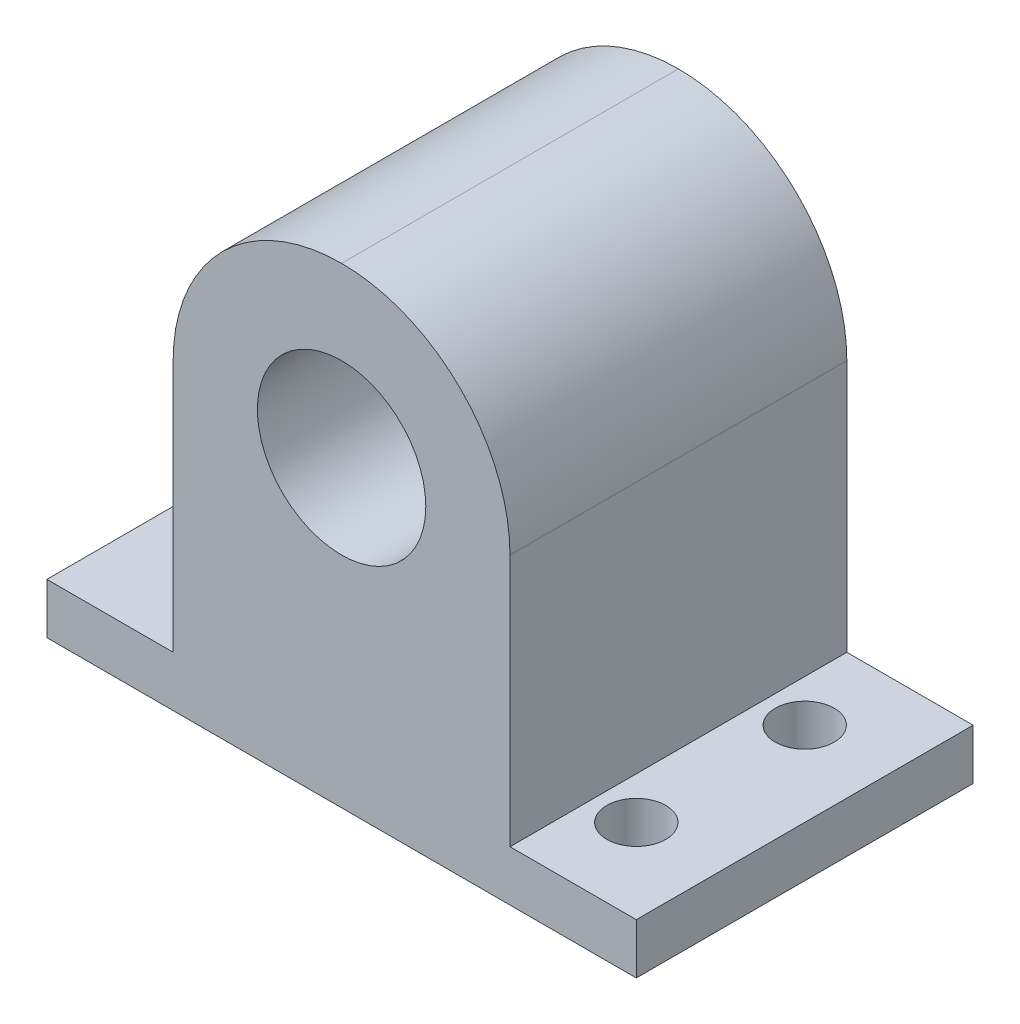
SolidWorks part; units mm, degrees
ref_plane "前视基准面" through (0, 0, 0) normal (0, 0, 1) x (1, 0, 0)
ref_plane "上视基准面" through (0, 0, 0) normal (0, 1, 0) x (1, 0, 0)
ref_plane "右视基准面" through (0, 0, 0) normal (1, 0, 0) x (0, 0, -1)
other "Configuration Table"
sketch "草图1" plane through (0, 0, 0) normal (0, 0, 1) x (1, 0, 0)
  line L1 (0, 0) -> (35, 0)
  line L2 (0, 0) -> (0, 3)
  line L3 (0, 3) -> (35, 3)
  line L4 (35, 0) -> (35, 3)
  line L5 (7.5, 3) -> (27.5, 3)
  line L6 (7.5, 3) -> (7.5, 28)
  line L7 (7.5, 28) -> (27.5, 28)
  line L8 (27.5, 3) -> (27.5, 28)
  dimension "D1" = 35
  dimension "D2" = 3
  dimension "D3" = 7.5
  dimension "D4" = 7.5
  dimension "D5" = 25
extrude "凸台-拉伸1" add sketch "草图1" along normal blind 20 contours L1 L4 L3 L2 | L7 L8 L5 L6 region at (17.5, 1.5, 0)
fillet "圆角1" radius 10 1 edges at (27.5, 28, 10)
fillet "圆角2" radius 10 1 edges at (7.5, 28, 10)
sketch "草图2" plane through (0, 0, 20) normal (0, 0, 1) x (1, 0, 0)
  line L2 (0, 3) -> (7.5, 3) construction
  line L3 (27.5, 3) -> (27.5, 18) construction
  circle A0 centre (17.5, 18) radius 5
  dimension "D1" = 10
  dimension "D2" = 15
  dimension "D3" = 10
extrude "切除-拉伸1" cut sketch "草图2" against normal up to next
sketch "草图4" plane through (0, 3, 0) normal (0, 1, 0) x (1, 0, 0)
  line L0 (0, -20) -> (35, -20) construction
  line L1 (0, 0) -> (35, 0) construction
  line L2 (35, -20) -> (35, 0) construction
  line L3 (0, -20) -> (0, 0) construction
  circle A0 centre (30, -15) radius 1.75
  circle A1 centre (30, -5) radius 1.75
  circle A2 centre (5, -15) radius 1.75
  circle A3 centre (5, -5) radius 1.75
  dimension "D1" = 3.5
  dimension "D2" = 3.5
  dimension "D3" = 3.5
  dimension "D4" = 3.5
  dimension "D5" = 5
  dimension "D6" = 5
  dimension "D7" = 5
  dimension "D8" = 5
  dimension "D9" = 5
extrude "切除-拉伸2" cut sketch "草图4" against normal up to next
sketch "草图3" plane through (0, 3, 0) normal (0, 1, 0) x (1, 0, 0)
  line L0 (0, 0) -> (7.5, 0) construction
  line L1 (27.5, 0) -> (35, 0) construction
  line L2 (0, -20) -> (0, 0) construction
  line L3 (35, -20) -> (35, 0) construction
  circle A0 centre (30, -5) radius 1.5
  circle A1 centre (5.0039, -5) radius 1.5
  dimension "D1" = 3
  dimension "D2" = 3
  dimension "D3" = 5
  dimension "D4" = 5
  dimension "D5" = 5.0039
  dimension "D6" = 5
